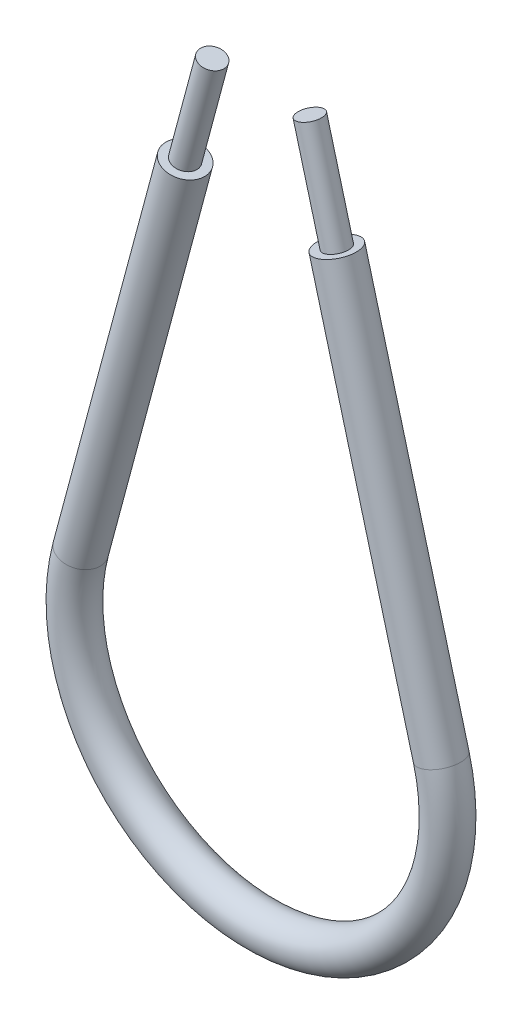
SolidWorks part; units mm, degrees
material "Galvanized Steel"
ref_plane "Front Plane" through (0, 0, 0) normal (0, 0, 1) x (1, 0, 0)
ref_plane "Top Plane" through (0, 0, 0) normal (0, 1, 0) x (1, 0, 0)
ref_plane "Right Plane" through (0, 0, 0) normal (1, 0, 0) x (0, 0, -1)
sketch "Sketch2" plane through (0, 0, 0) normal (0, 0, 1) x (1, 0, 0)
  line L0 (-114.3652, 4.5044) -> (-88.39, -92.4363)
  line L1 (-133.6438, 4.5044) -> (-159.619, -92.4363)
  line L2 (-16.7045, -37.25) -> (-231.3045, -37.25) construction
  line L3 (-104.9545, 6.35) -> (-143.0545, 6.35) construction
  line L4 (-105.3093, -6.2171) -> (-116.847, -9.3086) construction
  line L5 (-124.0045, 6.35) -> (-124.0045, -101.9792) construction
  arc A0 (-159.619, -92.4363) -> (-88.39, -92.4363) centre (-124.0045, -101.9792) ccw
  point P17 (-124.0045, -138.85)
  dimension "D1" = 101.6
ref_plane "Plane1" through (-114.3652, 4.5044, 0) normal (0.2588, -0.9659, 0) x (-0.9659, -0.2588, 0)
sketch "Sketch3" plane through (-114.3652, 4.5044, 0) normal (0.2588, -0.9659, 0) x (-0.9659, -0.2588, 0)
  circle A0 centre (0, 0) radius 2.3813
  dimension "D1" = 4.7625
sweep "Sweep1" add profiles "Sketch3" path "Sketch2"
sketch "Sketch4" plane through (-3.4457, 12.8596, 0) normal (0.2588, -0.9659, 0) x (0.9659, 0.2588, 0)
  circle A0 centre (-109.3024, 0) radius 3.9688
  circle A1 centre (-109.3024, 0) radius 2.3813
  dimension "D1" = 7.9375
  dimension "D2" = 4.7625
sketch "Sketch5" plane through (0, 0, 0) normal (0, 0, 1) x (1, 0, 0)
  line L0 (-133.6438, 4.5044) -> (-159.619, -92.4363) construction
  line L1 (-114.3652, 4.5044) -> (-88.39, -92.4363) construction
  line L2 (-138.9852, -15.4299) -> (-159.619, -92.4363)
  line L3 (-109.0238, -15.4299) -> (-88.39, -92.4363)
  line L4 (-111.3239, -16.0462) -> (-106.7237, -14.8136) construction
  arc A0 (-159.619, -92.4363) -> (-88.39, -92.4363) centre (-124.0045, -101.9792) ccw construction
  arc A1 (-159.619, -92.4363) -> (-88.39, -92.4363) centre (-124.0045, -101.9792) ccw
sweep "Sweep2" add profiles "Sketch4" path "Sketch5"
